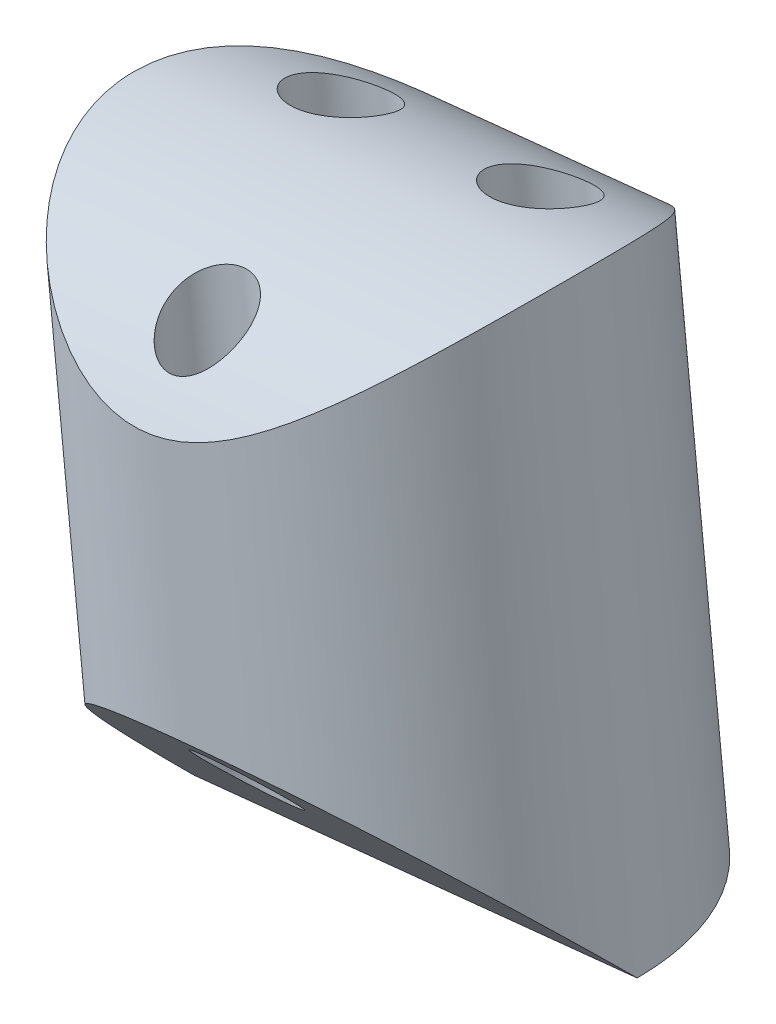
SolidWorks part; units mm, degrees
ref_plane "Front Plane" through (0, 0, 0) normal (0, 0, 1) x (1, 0, 0)
ref_plane "Top Plane" through (0, 0, 0) normal (0, 1, 0) x (1, 0, 0)
ref_plane "Right Plane" through (0, 0, 0) normal (1, 0, 0) x (0, 0, -1)
sketch "Sketch2" plane through (0, 0, 0) normal (0, 0, 1) x (1, 0, 0)
  line L0 (0, 0) -> (90, 0)
  line L1 (90, 0) -> (90, 120)
  line L2 (90, 120) -> (0, 120)
  line L3 (0, 120) -> (0, 0)
  line L4 (0, 120) -> (-10, 120)
  line L5 (-10, 120) -> (-10, 16.9491)
  line L6 (-10, 120) -> (57.5, 127)
  line L7 (57.5, 127) -> (90, 124)
  line L8 (90, 120) -> (99, 60)
  line L10 (90, 124) -> (90, 120)
  line L11 (5.9147, 0) -> (5.9147, -25)
  line L12 (5.9147, -25) -> (-4.0853, -25)
  line L13 (-4.0853, -29) -> (-4.0853, 0)
  line L14 (80, 0) -> (80, -25)
  line L15 (80, -25) -> (90, -25)
  line L16 (90, -29) -> (90, 0)
  line L17 (15.7927, 122.6748) -> (5.4776, 222.1414)
  line L18 (5.4776, 222.1414) -> (21.3923, 223.7918)
  line L19 (21.3923, 223.7918) -> (31.7073, 124.3252)
  line L20 (7.6492, 201.201) -> (23.5639, 202.8514)
  line L21 (10.9066, 169.7905) -> (26.8212, 171.441)
  line L22 (-10, 120) -> (-20.0396, 216.8108)
  line L23 (-20.0396, 216.8108) -> (-4.125, 218.4612)
  line L24 (-4.125, 218.4612) -> (5.9147, 121.6504)
  line L25 (-17.926, 196.4296) -> (-2.0114, 198.08)
  line L26 (-14.7556, 165.8578) -> (1.159, 167.5082)
  line L27 (57.5, 127) -> (46.9095, 229.1223)
  line L28 (46.9095, 229.1223) -> (30.9949, 227.4719)
  line L29 (30.9949, 227.4719) -> (41.5853, 125.3496)
  line L30 (33.2245, 205.9725) -> (49.1391, 207.6229)
  line L31 (36.5688, 173.7233) -> (52.4835, 175.3737)
  line L34 (90, 124) -> (99.1917, 223.5767)
  line L35 (99.1917, 223.5767) -> (83.2594, 225.0473)
  line L36 (83.2594, 225.0473) -> (74.0677, 125.4707)
  line L38 (81.3243, 204.0838) -> (97.2566, 202.6132)
  line L39 (78.4217, 172.6386) -> (94.354, 171.1679)
  line L40 (62.4078, 79.6749) -> (57.5, 127) construction
  line L41 (41.5853, 125.3496) -> (46.4931, 78.0244) construction
  line L42 (46.4931, 78.0244) -> (62.4078, 79.6749) construction
  line L43 (31.7073, 124.3252) -> (36.6151, 77.0001) construction
  line L44 (36.6151, 77.0001) -> (20.7005, 75.3496) construction
  line L45 (20.7005, 75.3496) -> (15.7927, 122.6748) construction
  line L46 (5.9147, 121.6504) -> (10.8224, 74.3253) construction
  line L47 (10.8224, 74.3253) -> (-5.0922, 72.6749) construction
  line L48 (-5.0922, 72.6749) -> (-10, 120) construction
  line L49 (74.0677, 125.4707) -> (69.6944, 78.0931) construction
  line L50 (69.6944, 78.0931) -> (85.7624, 78.0931) construction
  line L51 (85.7624, 78.0931) -> (90, 124) construction
  line L52 (-12.0823, 217.636) -> (10.4873, 0) construction
  line L53 (13.4349, 222.9666) -> (36.5574, 0) construction
  line L54 (38.9522, 228.2971) -> (62.6275, 0) construction
  line L55 (91.2256, 224.312) -> (70.5198, 0) construction
  line L59 (99, 60) -> (93.5277, 44.9649)
  line L60 (99, 60) -> (169.4769, 34.3485)
  line L61 (169.4769, 34.3485) -> (164.0046, 19.3134)
  line L62 (164.0046, 19.3134) -> (93.5277, 44.9649)
  line L63 (90, -2) -> (100, -2)
  line L64 (141.2862, 44.6091) -> (135.8138, 29.574)
  line L65 (99, 60) -> (55.7741, 75.7329) construction
  line L66 (55.7741, 75.7329) -> (50.3018, 60.6978) construction
  line L67 (100, -2) -> (100, -29)
  line L70 (-4.0853, -2) -> (-14.0853, -2)
  line L71 (-14.0853, -2) -> (-14.0853, -29)
  line L74 (-4.0853, 0) -> (0, 0)
  line L75 (-14.0853, -29) -> (-14.0853, -112.587)
  line L76 (-14.0853, -112.587) -> (100, -112.587)
  line L77 (100, -112.587) -> (100, -29)
  line L78 (-14.0853, -29) -> (100, -29)
  line L79 (-14.0853, -14.5) -> (100, -14.5) construction
  line L80 (31.7073, -112.587) -> (31.7073, -122.6232)
  line L81 (31.7073, -122.6232) -> (42.9573, -122.6232)
  line L82 (42.9573, -122.6232) -> (42.9573, -112.587)
  line L83 (-14.0853, -112.587) -> (-88.3667, -112.587)
  line L84 (-88.3667, -112.587) -> (-88.3667, -128.2699)
  line L85 (-88.3667, -128.2699) -> (169.4958, -128.2699)
  line L86 (169.4958, -128.2699) -> (169.4958, -112.587)
  line L87 (169.4958, -112.587) -> (100, -112.587)
  line L88 (90, 60) -> (-10, 60) construction
  line L89 (50.3018, 60.6978) -> (93.5277, 44.9649) construction
  line L90 (87.2806, 55.7521) -> (166.7408, 26.8309) construction
  line L91 (87.2806, 55.7521) -> (82.1749, 52.5336) construction
  line L92 (82.1749, 52.5336) -> (77.3257, 0) construction
  line L93 (83.1185, 56.6957) -> (86.337, 51.59) construction
  arc A0 (-10, 16.9491) -> (-4.0853, 0) centre (14.9876, 16.1624) ccw
  arc A1 (93.5277, 44.9649) -> (90, 0) centre (-126.4069, 39.5988) cw
  point P42 (41.1818, 206.7977)
  point P100 (84.7278, 54.1428)
  point P101 (84.7278, 54.1428)
  dimension "D11" = 47.3684
  dimension "D35" = 9
  dimension "D32" = 220
  dimension "D36" = 25
  dimension "D1" = 120
  dimension "D2" = 90
  dimension "D3" = 10
  dimension "D5" = 67.862
  dimension "D6" = 7
  dimension "D7" = 4
  dimension "D8" = 16
  dimension "D9" = 16
  dimension "D10" = 100
  dimension "D12" = 31.5789
  dimension "D13" = 16
  dimension "D14" = 16
  dimension "D15" = 16
  dimension "D16" = 25.7927
  dimension "D17" = 100
  dimension "D18" = 21.0526
  dimension "D19" = 31.5789
  dimension "D20" = 97.33
  dimension "D21" = 102.67
  dimension "D22" = 20.4905
  dimension "D23" = 30.7358
  dimension "D24" = 21.6147
  dimension "D25" = 32.4221
  dimension "D26" = 25
  dimension "D28" = 25
  dimension "D29" = 75
  dimension "D30" = 47.5789
  dimension "D31" = 30
  dimension "D33" = 46
  dimension "D34" = 20
  dimension "D37" = 2
  dimension "D38" = 2
  dimension "D39" = 27
  dimension "D40" = 10
  dimension "D41" = 10
  dimension "D42" = 27
  dimension "D43" = 14.5
  dimension "D44" = 127.5
ref_plane "Plane1" through (87.2806, 55.7521, 0) normal (-0.846, -0.5333, 0) x (0, 0, 1)
ref_plane "Plane2" through (82.1749, 52.5336, 0) normal (-0.0919, -0.9958, 0) x (-0.9958, 0.0919, 0)
ref_plane "Plane3" through (91.2256, 224.312, 0) normal (-0.0919, -0.9958, 0) x (-0.9958, 0.0919, 0)
ref_plane "Plane4" through (38.9522, 228.2971, 0) normal (0.1032, -0.9947, 0) x (-0.9947, -0.1032, 0)
ref_plane "Plane5" through (13.4349, 222.9666, 0) normal (0.1032, -0.9947, 0) x (-0.9947, -0.1032, 0)
ref_plane "Plane7" through (166.7408, 26.8309, 0) normal (0.9397, -0.342, 0) x (0, 0, -1)
ref_plane "Plane8" through (110.4217, -40.1902, 0) normal (0.9397, -0.342, 0) x (0, 0, -1)
ref_plane "Plane9" through (19.3664, 209.803, 0) normal (-0.0919, -0.9958, 0) x (-0.9958, 0.0919, 0)
ref_plane "Plane10" through (16.4638, 178.3578, 0) normal (-0.0919, -0.9958, 0) x (-0.9958, 0.0919, 0)
ref_plane "Plane11" through (-20.7793, 200.3721, 0) normal (0.1032, -0.9947, 0) x (-0.9947, -0.1032, 0)
ref_plane "Plane12" through (-17.435, 168.1229, 0) normal (0.1032, -0.9947, 0) x (-0.9947, -0.1032, 0)
ref_plane "Plane13" through (-20.5619, 198.2754, 0) normal (0.1032, -0.9947, 0) x (-0.9947, -0.1032, 0)
ref_plane "Plane14" through (-17.3045, 166.8649, 0) normal (0.1032, -0.9947, 0) x (-0.9947, -0.1032, 0)
ref_plane "Plane15" through (-12.0823, 217.636, 0) normal (0.1032, -0.9947, 0) x (-0.9947, -0.1032, 0)
ref_plane "Plane16" through (-20.3445, 196.1788, 0) normal (0.1032, -0.9947, 0) x (-0.9947, -0.1032, 0)
ref_plane "Plane17" through (-17.1741, 165.607, 0) normal (0.1032, -0.9947, 0) x (-0.9947, -0.1032, 0)
ref_plane "Plane18" through (12.1098, 131.1899, 0) normal (-0.0919, -0.9958, 0) x (-0.9958, 0.0919, 0)
ref_plane "Plane19" through (-12.4184, 119.7492, 0) normal (0.1032, -0.9947, 0) x (-0.9947, -0.1032, 0)
ref_plane "Plane20" through (0, 0, 0) normal (0, 0, 1) x (0.1032, -0.9947, 0)
ref_plane "Plane21" through (0, 0, 0) normal (0, 0, 1) x (-0.0919, -0.9958, 0)
ref_plane "Plane22" through (10.3758, 1.076, 0) normal (-0.9947, -0.1032, 0) x (0.1032, -0.9947, 0)
ref_plane "Plane23" through (36.1684, 3.7508, 0) normal (-0.9947, -0.1032, 0) x (0.1032, -0.9947, 0)
ref_plane "Plane24" through (61.9611, 6.4256, 0) normal (-0.9947, -0.1032, 0) x (0.1032, -0.9947, 0)
ref_plane "Plane25" through (69.924, -6.4545, 0) normal (-0.9958, 0.0919, 0) x (-0.0919, -0.9958, 0)
sketch "Sketch3" plane through (-12.0823, 217.636, 0) normal (0.1032, -0.9947, 0) x (-0.9947, -0.1032, 0)
  circle A0 centre (0, 0) radius 8
  dimension "D1" = 16
extrude "Boss-Extrude1" add sketch "Sketch3" along normal blind 21.0526
sketch "Sketch4" plane through (10.3758, 1.076, 0) normal (-0.9947, -0.1032, 0) x (0.1032, -0.9947, 0)
  line L0 (-217.7214, 8) -> (-213.7214, 8)
  line L1 (-196.6688, 8) -> (-217.7214, 8) construction
  line L2 (-217.7214, 8) -> (-217.7214, -8)
  line L3 (-217.7214, -8) -> (-213.7214, -8)
  line L4 (-217.7214, -8) -> (-196.6688, -8) construction
  arc A0 (-213.7214, 8) -> (-213.7214, -8) centre (-207.3937, 0) ccw
  dimension "D2" = 10.2
  dimension "D1" = 4
extrude "Cut-Extrude1" cut sketch "Sketch4" against normal through all and the other way through all
sketch "Sketch5" plane through (10.3758, 1.076, 0) normal (-0.9947, -0.1032, 0) x (0.1032, -0.9947, 0)
  line L0 (-196.6688, 0) -> (-204.6688, 8)
  line L1 (-196.6688, -8) -> (-196.6688, 8) construction
  line L2 (-196.6688, 8) -> (-213.7214, 8) construction
  line L3 (-204.6688, 8) -> (-196.6688, 8)
  line L4 (-196.6688, 8) -> (-196.6688, 0)
  dimension "D1" = 45
extrude "Cut-Extrude2" cut sketch "Sketch5" against normal through all and the other way through all
sketch "Sketch7" plane through (10.3758, 1.076, 0) normal (-0.9947, -0.1032, 0) x (0.1032, -0.9947, 0)
  line L2 (-192.6688, 0) -> (-196.6688, -4)
  line L5 (-200.6688, 4) -> (-196.6688, 0)
  line L6 (-196.6688, 0) -> (-204.6688, 8) construction
  line L8 (-213.7055, 0) -> (7.2742, 0) construction
  line L9 (-192.6688, 0) -> (-192.6688, 4)
  line L10 (-192.6688, 4) -> (-200.6688, 4)
  line L11 (-196.6688, 0) -> (-192.6688, 4) construction
  line L12 (-196.6688, -8) -> (-196.6688, 0) construction
  line L13 (-196.6688, 0) -> (-196.6688, -4)
  dimension "D1" = 45
sketch "Sketch8" plane through (-12.0823, 217.636, 0) normal (0.1032, -0.9947, 0) x (-0.9947, -0.1032, 0)
  line L0 (8, 0) -> (-8, 0) construction
  circle A0 centre (-3.6, 3) radius 1.6
  circle A1 centre (3.6, 3) radius 1.6
  circle A3 centre (0, -5.5) radius 1.4
  point P6 (0, 0)
  dimension "D1" = 3.2
  dimension "D2" = 3.2
  dimension "D7" = 2.8
  dimension "D3" = 3
  dimension "D4" = 3
  dimension "D5" = 3.6
  dimension "D6" = 3.6
  dimension "D8" = 5.5
extrude "Cut-Extrude3" cut sketch "Sketch8" against normal through all and the other way through all
sketch "Sketch9" plane through (-20.2865, 195.6197, 0) normal (0.1032, -0.9947, 0) x (0.9947, 0.1032, 0)
  line L0 (4.5289, -5.4) -> (16.3339, -5.4)
  line L1 (2.4314, 0) -> (18.4314, 0) construction
  arc A0 (2.4314, 0) -> (18.4314, 0) centre (10.4314, 0) ccw construction
  arc A1 (4.5289, -5.4) -> (16.3339, -5.4) centre (10.4314, 0) ccw
  dimension "D1" = 5.4
